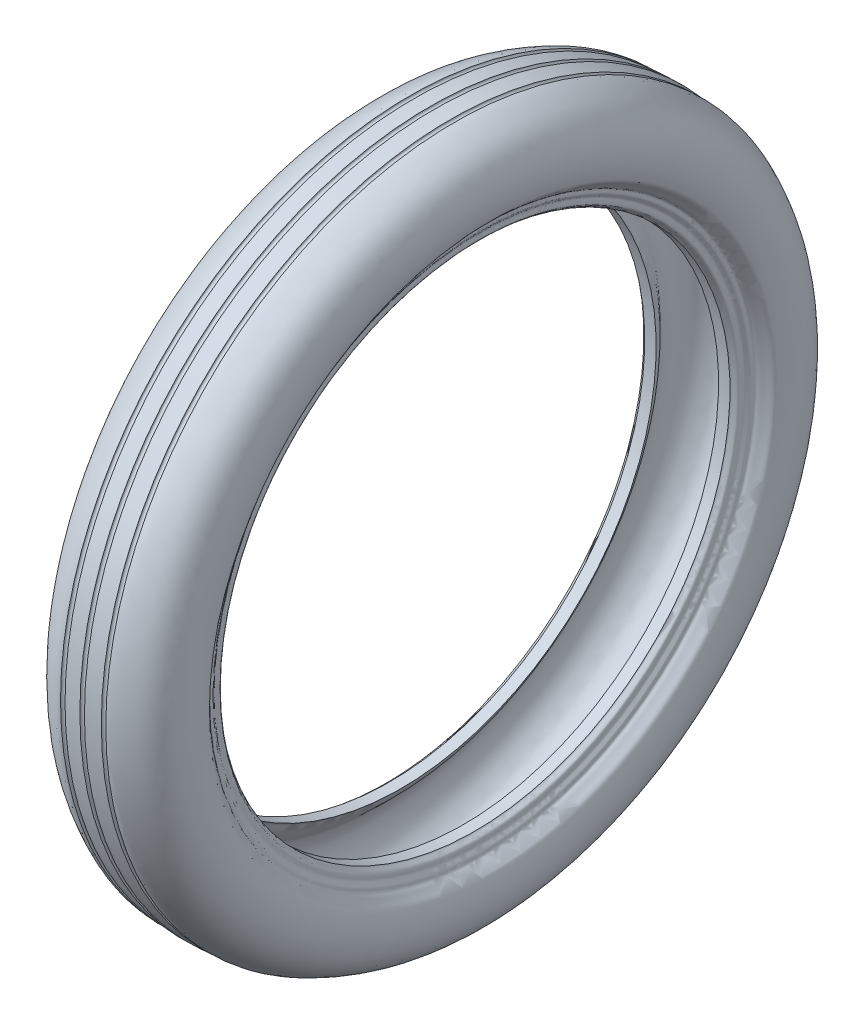
SolidWorks part; units mm, degrees
material "BUTYL"
ref_plane "Front Plane" through (0, 0, 0) normal (0, 0, 1) x (1, 0, 0)
ref_plane "Top Plane" through (0, 0, 0) normal (0, 1, 0) x (1, 0, 0)
ref_plane "Right Plane" through (0, 0, 0) normal (1, 0, 0) x (0, 0, -1)
sketch "Sketch1" plane through (0, 0, 0) normal (0, 0, 1) x (1, 0, 0)
  line L0 (51.6667, 341.5) -> (258.3333, 341.5) construction
  line L1 (43.3333, 103) -> (216.6667, 103) construction
  line L2 (0, 248.8346) -> (0, 0) construction
  line L3 (-24.8173, 203) -> (-33.9053, 203)
  line L4 (-14.4302, 277.4968) -> (-1.8191, 278.3033)
  line L5 (24.8173, 203) -> (33.9053, 203)
  line L6 (14.4302, 277.4968) -> (1.8191, 278.3033)
  line L7 (-102.7229, 0) -> (130.3407, 0) construction
  line L8 (-24.8173, 203) -> (24.8173, 203) construction
  arc A0 (-18.0013, 277.4968) -> (-14.4302, 277.4968) centre (-16.2157, 277.4968) ccw
  arc A1 (18.0013, 277.4968) -> (14.4302, 277.4968) centre (16.2157, 277.4968) cw
  arc A2 (-1.8191, 278.3033) -> (1.8191, 278.3033) centre (0, 278.3033) ccw
  spline S0 degree 3 poles (-24.8173, 203) (-27.2284, 205.0639) (-28.5496, 210.3276) (-33.6713, 215.0194) (-37.7773, 219.0104) (-42.2634, 223.062) (-45.1671, 229.5539) (-48.0287, 236.6578) (-47.888, 244.8825) (-46.3949, 254.0571) (-40.3487, 261.4036) (-33.8515, 268.8109) (-25.2444, 271.405) (-16.7423, 273.1864) (-10.1406, 273.4632) (-4.5443, 274.0141) (-1.7534, 273.4453) (0, 273.6518) knots 0 0 0 0 0.082233 0.137617 0.183009 0.237254 0.29747 0.371716 0.440605 0.515818 0.616104 0.690267 0.776014 0.84938 0.924773 0.95299 1 1 1 1
  spline S1 degree 3 poles (24.8173, 203) (27.2284, 205.0639) (28.5496, 210.3276) (33.6713, 215.0194) (37.7773, 219.0104) (42.2634, 223.062) (45.1671, 229.5539) (48.0287, 236.6578) (47.888, 244.8825) (46.3949, 254.0571) (40.3487, 261.4036) (33.8515, 268.8109) (25.2444, 271.405) (16.7423, 273.1864) (10.1406, 273.4632) (4.5443, 274.0141) (1.7534, 273.4453) (0, 273.6518) knots 0 0 0 0 0.082233 0.137617 0.183009 0.237254 0.29747 0.371716 0.440605 0.515818 0.616104 0.690267 0.776014 0.84938 0.924773 0.95299 1 1 1 1
  spline S2 degree 3 poles (-33.9053, 203) (-34.4514, 204.2233) (-38.4052, 205.2108) (-37.5895, 208.7025) (-37.3177, 211.6374) (-40.3679, 213.4652) (-39.0661, 217.0868) (-42.53, 218.9871) (-44.4812, 222.025) (-48.1613, 224.6642) (-49.3373, 231.2973) (-50.566, 239.2176) (-49.5419, 249.3098) (-46.4258, 258.7858) (-40.6849, 266.454) (-33.8688, 271.5447) (-26.5849, 275.2395) (-21.385, 277.7704) (-18.0013, 277.4968) knots 0 0 0 0 0.050285 0.080964 0.097206 0.139297 0.164562 0.195188 0.24242 0.280703 0.328072 0.440671 0.53315 0.638161 0.74644 0.823682 0.899585 1 1 1 1
  spline S3 degree 3 poles (33.9053, 203) (34.4514, 204.2233) (38.4052, 205.2108) (37.5895, 208.7025) (37.3177, 211.6374) (40.3679, 213.4652) (39.0661, 217.0868) (42.53, 218.9871) (44.4812, 222.025) (48.1613, 224.6642) (49.3373, 231.2973) (50.566, 239.2176) (49.5419, 249.3098) (46.4258, 258.7858) (40.6849, 266.454) (33.8688, 271.5447) (26.5849, 275.2395) (21.385, 277.7704) (18.0013, 277.4968) knots 0 0 0 0 0.050285 0.080964 0.097206 0.139297 0.164562 0.195188 0.24242 0.280703 0.328072 0.440671 0.53315 0.638161 0.74644 0.823682 0.899585 1 1 1 1
  dimension "D1" = 203
  dimension "D2" = 278.3033
revolve "Revolve2" add sketch "Sketch1" angle 360 about L7
sketch "Sketch3" plane through (0, 0, 0) normal (1, 0, 0) x (0, 0, -1)
  line L0 (0, 0) -> (0, -276.86)
  line L1 (0, -276.86) -> (50.8, -276.86)
  line L2 (50.8, -276.86) -> (40.8, -276.86)
  line L3 (50.8, -276.86) -> (50.8, -270.86)
  line L4 (40.8, -276.86) -> (40.8, -270.86)
  line L5 (50.8, -270.86) -> (40.8, -270.86)
  line L6 (50.8, -276.86) -> (60.8, -276.86)
  line L7 (50.8, -276.86) -> (50.8, -270.86)
  line L8 (60.8, -276.86) -> (60.8, -270.86)
  line L9 (50.8, -270.86) -> (60.8, -270.86)
  dimension "D1" = 276.86
  dimension "D2" = 50.8
  dimension "D3" = 6
  dimension "D4" = 10
  dimension "D5" = 10
ref_plane "Plane1" through (24.8173, 0, 0) normal (1, 0, 0) x (0, 0, -1)
ref_plane "Plane2" through (-24.8173, 0, 0) normal (1, 0, 0) x (0, 0, -1)
ref_plane "Plane3" through (0, 0, 0) normal (1, 0, 0) x (0, 0, -1)
move or copy body "Body-Move/Copy2" [suppressed] bodies to move or copy 102
move or copy body "Body-Move/Copy1" [suppressed] bodies to move or copy 102
